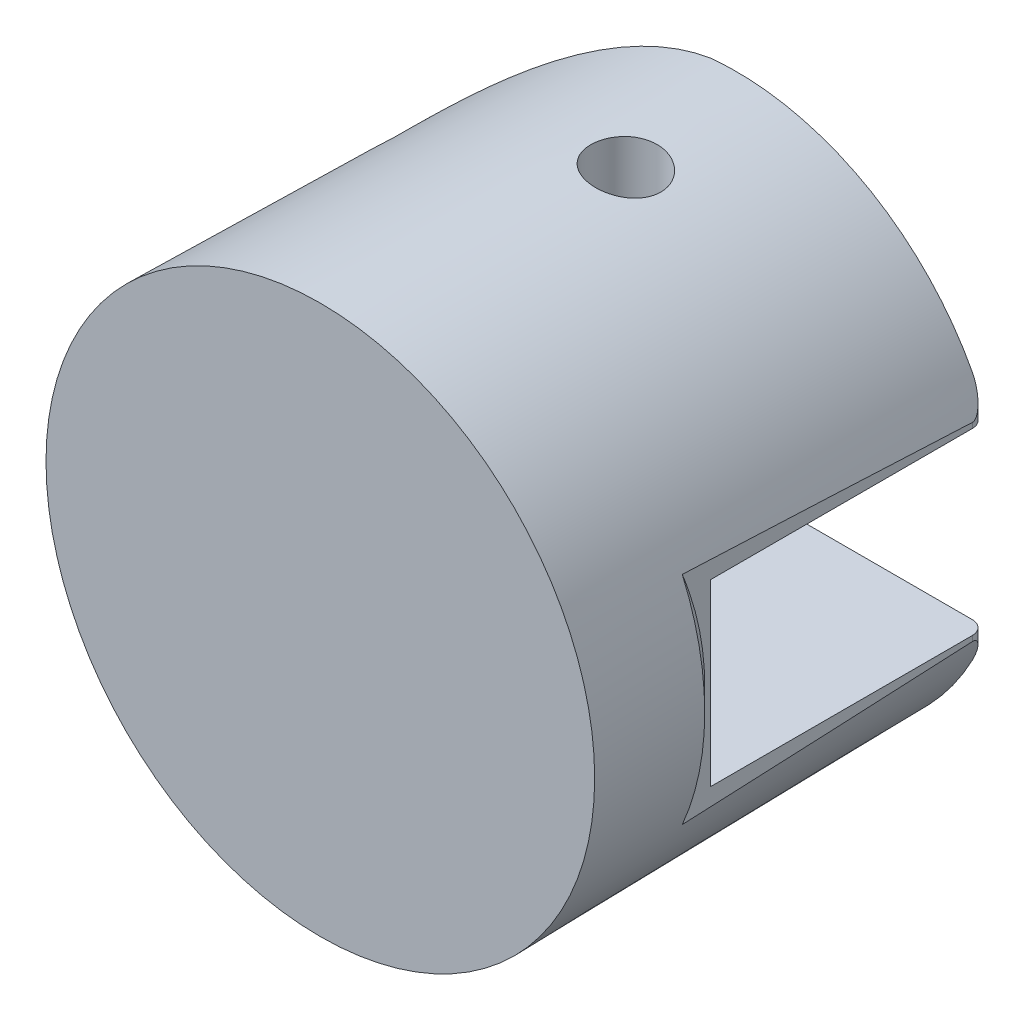
SolidWorks part; units mm, degrees
ref_plane "Front Plane" through (0, 0, 0) normal (0, 0, 1) x (1, 0, 0)
ref_plane "Top Plane" through (0, 0, 0) normal (0, 1, 0) x (1, 0, 0)
ref_plane "Right Plane" through (0, 0, 0) normal (1, 0, 0) x (0, 0, -1)
sketch "Sketch1" plane through (0, 0, 0) normal (0, 0, 1) x (1, 0, 0)
  circle A0 centre (0, 0) radius 10
  dimension "D1" = 20
extrude "Boss-Extrude1" add sketch "Sketch1" along normal blind 18
sketch "Sketch2" plane through (0, 0, 0) normal (0, 1, 0) x (1, 0, 0)
  line L13 (9.0632, -10) -> (9.0632, 0)
  line L14 (-8, -10) -> (-7.3121, -5.8413)
  line L15 (9.0632, 0) -> (-0.8843, 0)
  line L16 (-8, -10) -> (-11.2528, -10)
  line L17 (-11.2528, -10) -> (-11.2528, 2.5986)
  line L18 (-11.2528, 2.5986) -> (12.4635, 2.5986)
  line L19 (12.4635, 2.5986) -> (12.4635, -10)
  line L20 (12.4635, -10) -> (9.0632, -10)
  line L21 (-10, -18) -> (10, -18) construction
  line L22 (-10, 0) -> (-10, -18) construction
  line L23 (10, 0) -> (-10, 0) construction
  arc A1 (-0.8843, 0) -> (-7.3121, -5.8413) centre (-0.4059, -6.9836) ccw
  dimension "D1" = 2.4635
  dimension "D3" = 7
  dimension "D2" = 1.2528
  dimension "D4" = 8
  dimension "D5" = 2
  dimension "D6" = 12.5986
  dimension "D7" = 10
  dimension "D8" = 3.4003
  dimension "D9" = 4.2153
  dimension "D10" = 23.7163
extrude "Cut-Extrude1" cut sketch "Sketch2" against normal through all both and the other way through all
sketch "Sketch3" plane through (0, 0, 0) normal (0, 1, 0) x (1, 0, 0)
  line L0 (1, -5) -> (1, -10.609) construction
  line L2 (-10, -18) -> (10, -18) construction
  circle A1 centre (1, -5) radius 1.25
  dimension "D1" = 2.5
  dimension "D2" = 9
  dimension "D3" = 13
extrude "Cut-Extrude2" cut sketch "Sketch3" against normal through all both and the other way through all
sketch "Sketch4" plane through (0, 0, 18) normal (0, 0, 1) x (1, 0, 0)
  circle A0 centre (0, 0) radius 10 construction
  circle A1 centre (0, 0) radius 10
extrude "Cut-Extrude-Thin1" cut sketch "Sketch4" against normal blind 23.25 draft 1 and the other way through all thin draft outward yes thin type one direction wall 10
fillet "Fillet1" radius 0.5 1 edges at (9.0632, 0, 0)
chamfer "Chamfer1" distance 1 angle 45 1 edges at (9.8604, 0, 10) first distance on face at (9.4618, 0, 10)
sketch "Sketch5" plane through (0, 0, 0) normal (0, 1, 0) x (1, 0, 0)
  line L0 (9.0632, -11.0178) -> (9.0632, -0.5) construction
  line L1 (9.0632, -10) -> (-7.9968, -10)
  line L2 (9.0632, -10) -> (9.0632, 1.0009)
  line L3 (9.0632, 1.0009) -> (-7.9968, 1.0009)
  line L4 (-7.9968, -10) -> (-7.9968, 1.0009)
  line L5 (-8, -10) -> (-9.8604, -10) construction
  dimension "D1" = 11.0009
  dimension "D2" = 17.06
extrude "Cut-Extrude3" cut sketch "Sketch5" against normal blind 3.25 and the other way blind 3.25
sketch "Sketch6" plane through (0, 0, 0) normal (0, 1, 0) x (1, 0, 0)
  line L0 (-10, -18) -> (10, -18) construction
  line L1 (-12.0127, -15.0797) -> (11.4257, -15.0797)
  line L2 (-12.0127, -15.0797) -> (-12.0127, -19.9016)
  line L3 (-12.0127, -19.9016) -> (11.4257, -19.9016)
  line L4 (11.4257, -15.0797) -> (11.4257, -19.9016)
  dimension "D1" = 23.4384
  dimension "D2" = 4.8219
  dimension "D3" = 1.9016
  dimension "D4" = 2.0127
extrude "Cut-Extrude4" cut sketch "Sketch6" against normal blind 15.25 and the other way blind 17
